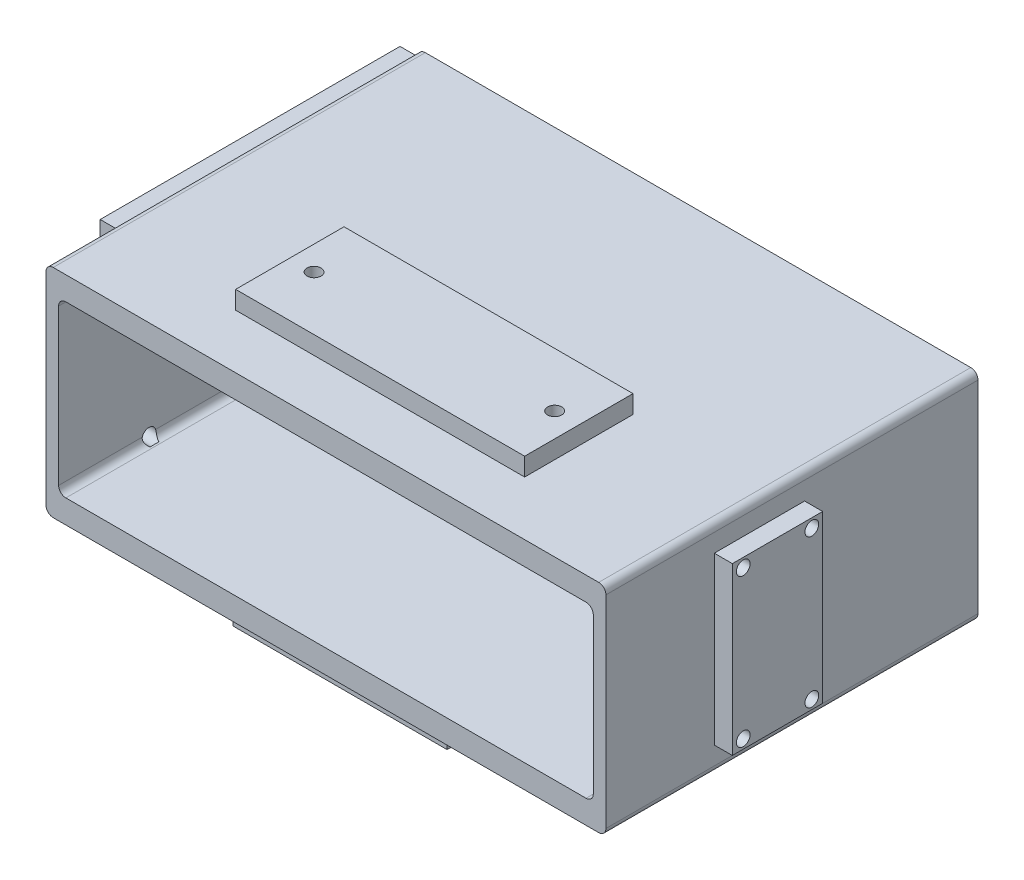
SolidWorks part; units mm, degrees
ref_plane "前视基准面" through (0, 0, 0) normal (0, 0, 1) x (1, 0, 0)
ref_plane "上视基准面" through (0, 0, 0) normal (0, 1, 0) x (1, 0, 0)
ref_plane "右视基准面" through (0, 0, 0) normal (1, 0, 0) x (0, 0, -1)
sketch "草图1" plane through (0, 0, 0) normal (0, 0, 1) x (1, 0, 0)
  line L1 (-77.5, -30) -> (77.5, -30)
  line L2 (-77.5, -30) -> (-77.5, 30)
  line L3 (-77.5, 30) -> (77.5, 30)
  line L4 (77.5, -30) -> (77.5, 30)
  line L5 (-77.5, -30) -> (77.5, 30) construction
  line L6 (-77.5, 30) -> (77.5, -30) construction
  point P0 (0, 0)
  dimension "D1" = 60
  dimension "D2" = 155
extrude "凸台-拉伸1" add sketch "草图1" along normal blind 3
sketch "草图2" plane through (0, 0, 3) normal (0, 0, 1) x (1, 0, 0)
  line L5 (-75.8502, 29.3614) -> (77.5, -30) construction
  line L6 (-81.3153, 0) -> (81.3153, 0) construction
  line L7 (-74, 23.5) -> (74, 23.5)
  line L8 (-74, 23.5) -> (-74, -23.5)
  line L9 (-74, -23.5) -> (74, -23.5)
  line L10 (74, 23.5) -> (74, -23.5)
  line L11 (-74, 23.5) -> (74, -23.5) construction
  line L12 (-74, -23.5) -> (74, 23.5) construction
  line L20 (77.5, -30) -> (77.5, 30)
  line L21 (77.5, 30) -> (-77.5, 30)
  line L22 (-77.5, 30) -> (-77.5, -30)
  line L23 (-77.5, -30) -> (77.5, -30)
  line L24 (77.5, -30) -> (77.5, 30)
  line L25 (77.5, 30) -> (-77.5, 30)
  line L26 (-77.5, 30) -> (-77.5, -30)
  line L27 (-77.5, -30) -> (77.5, -30)
  point P0 (0, 0)
  point P5 (0, 0)
  dimension "D1" = 148
  dimension "D2" = 47
  dimension "D3" = 0
extrude "凸台-拉伸2" add sketch "草图2" along normal blind 90
fillet "圆角1" radius 2 8 edges at (-77.5, 30, 46.5) (-77.5, -30, 46.5) (77.5, 30, 46.5) (77.5, -30, 46.5) (74, -23.5, 48) (-74, -23.5, 48) (74, 23.5, 48) (-74, 23.5, 48)
sketch "草图5" plane through (0, 0, 0) normal (0, 0, -1) x (-1, 0, 0)
  line L4 (77.5, -28) -> (77.5, 28)
  line L5 (75.5, 30) -> (-75.5, 30)
  line L6 (-77.5, 28) -> (-77.5, -28)
  line L7 (-75.5, -30) -> (75.5, -30)
  line L8 (77.5, -28) -> (77.5, 28)
  line L9 (75.5, 30) -> (-75.5, 30)
  line L10 (-77.5, 28) -> (-77.5, -28)
  line L11 (-75.5, -30) -> (75.5, -30)
  circle A0 centre (-60, 15) radius 1.9
  circle A1 centre (-60, -15) radius 1.9
  circle A2 centre (-30, 15) radius 1.9
  circle A3 centre (-30, -15) radius 1.9
  circle A4 centre (0, 15) radius 1.9
  arc A5 (77.5, 28) -> (75.5, 30) centre (75.5, 28) ccw
  arc A6 (-75.5, 30) -> (-77.5, 28) centre (-75.5, 28) ccw
  arc A7 (-77.5, -28) -> (-75.5, -30) centre (-75.5, -28) ccw
  arc A8 (75.5, -30) -> (77.5, -28) centre (75.5, -28) ccw
  arc A9 (77.5, 28) -> (75.5, 30) centre (75.5, 28) ccw
  arc A10 (-75.5, 30) -> (-77.5, 28) centre (-75.5, 28) ccw
  arc A11 (-77.5, -28) -> (-75.5, -30) centre (-75.5, -28) ccw
  arc A12 (75.5, -30) -> (77.5, -28) centre (75.5, -28) ccw
  circle A13 centre (0, -15) radius 1.9
  circle A14 centre (30, 15) radius 1.9
  circle A15 centre (30, -15) radius 1.9
  circle A16 centre (60, 15) radius 1.9
  circle A17 centre (60, -15) radius 1.9
  dimension "D1" = 3.8
  dimension "D4" = 17.5
  dimension "D3" = 15
  dimension "D6" = 30
  dimension "D8" = 30
  dimension "D2" = 0
  dimension "D5" = 2
  dimension "D7" = 5
extrude "切除-拉伸2" cut sketch "草图5" against normal blind 3 contours A0 | A1 | A3 | A2 | A4 | A13 | A14 | A15 | A16 | A17
sketch "草图6" plane through (-77.5, 0, 0) normal (-1, 0, 0) x (0, 0, 1)
  line L0 (93, 28) -> (93, -28) construction
  line L1 (24, -22) -> (68, -22)
  line L2 (24, -22) -> (24, 22)
  line L3 (24, 22) -> (68, 22)
  line L4 (68, -22) -> (68, 22)
  line L5 (24, -22) -> (68, 22) construction
  line L6 (24, 22) -> (68, -22) construction
  line L7 (93, 0) -> (0, 0)
  line L8 (0, 28) -> (0, -28) construction
  circle A0 centre (68, -22) radius 1.9
  circle A1 centre (68, 22) radius 1.9
  circle A2 centre (24, 22) radius 1.9
  circle A3 centre (24, -22) radius 1.9
  point P0 (46, 0)
  dimension "D4" = 3.8
  dimension "D5" = 3.8
  dimension "D6" = 3.8
  dimension "D7" = 3.8
  dimension "D1" = 44
  dimension "D2" = 44
  dimension "D3" = 25
extrude "切除-拉伸3" cut sketch "草图6" against normal blind 5 contours L4 A1 L3 | L3 A1 L4 | L3 A2 L2 | L2 A2 L3 | L1 A0 L4 | L4 A0 L1 | L2 A3 L1 | L1 A3 L2 region at (-77.5, -21.1936, 24.8064) region at (-77.5, -22.2688, 23.7312) region at (-77.5, -21.1936, 67.1936) region at (-77.5, -22.2688, 68.2688) region at (-77.5, 22.2688, 23.7312) region at (-77.5, 21.1936, 24.8064) region at (-77.5, 21.1936, 67.1936) region at (-77.5, 22.2688, 68.2688)
sketch "草图9" plane through (0, 0, 0) normal (0, 0, -1) x (-1, 0, 0)
  line L4 (77.5, -28) -> (77.5, 28)
  line L5 (75.5, 30) -> (-75.5, 30)
  line L6 (-77.5, 28) -> (-77.5, -28)
  line L7 (-75.5, -30) -> (75.5, -30)
  line L8 (77.5, -28) -> (77.5, 28)
  line L9 (75.5, 30) -> (-75.5, 30)
  line L10 (-77.5, 28) -> (-77.5, -28)
  line L11 (-75.5, -30) -> (75.5, -30)
  circle A1 centre (-60, 15) radius 1.9
  circle A2 centre (-60, 15) radius 1.9
  circle A3 centre (60, -15) radius 1.9
  circle A4 centre (60, -15) radius 1.9
  circle A5 centre (-60, -15) radius 1.9
  circle A6 centre (-60, -15) radius 1.9
  circle A7 centre (-30, -15) radius 1.9
  circle A8 centre (-30, -15) radius 1.9
  circle A9 centre (-30, 15) radius 1.9
  circle A10 centre (-30, 15) radius 1.9
  circle A11 centre (0, 15) radius 1.9
  circle A12 centre (0, 15) radius 1.9
  circle A13 centre (60, 15) radius 1.9
  circle A14 centre (60, 15) radius 1.9
  circle A15 centre (30, -15) radius 1.9
  circle A16 centre (30, -15) radius 1.9
  circle A17 centre (30, 15) radius 1.9
  circle A18 centre (30, 15) radius 1.9
  circle A19 centre (0, -15) radius 1.9
  circle A20 centre (0, -15) radius 1.9
  arc A24 (77.5, 28) -> (75.5, 30) centre (75.5, 28) ccw
  arc A25 (-75.5, 30) -> (-77.5, 28) centre (-75.5, 28) ccw
  arc A26 (-77.5, -28) -> (-75.5, -30) centre (-75.5, -28) ccw
  arc A27 (75.5, -30) -> (77.5, -28) centre (75.5, -28) ccw
  arc A28 (77.5, 28) -> (75.5, 30) centre (75.5, 28) ccw
  arc A29 (-75.5, 30) -> (-77.5, 28) centre (-75.5, 28) ccw
  arc A30 (-77.5, -28) -> (-75.5, -30) centre (-75.5, -28) ccw
  arc A31 (75.5, -30) -> (77.5, -28) centre (75.5, -28) ccw
  dimension "D1" = 0
  dimension "D2" = 0
  dimension "D3" = 0
  dimension "D4" = 0
  dimension "D5" = 0
  dimension "D6" = 0
  dimension "D7" = 0
  dimension "D8" = 0
  dimension "D9" = 0
  dimension "D10" = 0
  dimension "D11" = 0
extrude "凸台-拉伸3" add sketch "草图9" along normal blind 10
sketch "草图10" plane through (-77.5, 0, 0) normal (-1, 0, 0) x (0, 0, 1)
  line L0 (93, 28) -> (-10, 28) construction
  line L1 (73, 28) -> (-10, 28)
  line L2 (73, 28) -> (73, -28)
  line L3 (73, -28) -> (-10, -28)
  line L4 (-10, 28) -> (-10, -28)
  circle A0 centre (68, 22) radius 1.9 construction
  circle A2 centre (24, -22) radius 1.9
  circle A4 centre (24, -22) radius 1.9
  circle A6 centre (24, 22) radius 1.9
  circle A8 centre (24, 22) radius 1.9
  circle A10 centre (68, -22) radius 1.9
  circle A11 centre (68, -22) radius 1.9
  circle A12 centre (68, 22) radius 1.9
  circle A13 centre (68, 22) radius 1.9
  dimension "D1" = 5
  dimension "D2" = 0
  dimension "D3" = 0
  dimension "D4" = 0
  dimension "D5" = 0
extrude "凸台-拉伸4" add sketch "草图10" along normal blind 5
sketch "草图7" plane through (0, -30, 0) normal (0, -1, 0) x (1, 0, 0)
  line L0 (-75.5, 41.5) -> (75.5, 41.5)
  line L1 (-24.605, -3) -> (24.605, -3)
  line L2 (-24.605, -3) -> (-24.605, 84.08)
  line L3 (-24.605, 84.08) -> (24.605, 84.08)
  line L4 (24.605, -3) -> (24.605, 84.08)
  line L5 (-24.605, -3) -> (24.605, 84.08) construction
  line L6 (-24.605, 84.08) -> (24.605, -3) construction
  line L7 (-75.5, 93) -> (-75.5, -10) construction
  line L8 (75.5, -10) -> (75.5, 93) construction
  line L9 (75.5, -10) -> (-75.5, -10) construction
  line L12 (0, 93) -> (0, -10)
  line L13 (-75.5, 93) -> (75.5, 93) construction
  circle A0 centre (24.605, 84.08) radius 1.9
  circle A1 centre (-24.605, 84.08) radius 1.9
  circle A2 centre (-24.605, -3) radius 1.9
  circle A3 centre (24.605, -3) radius 1.9
  point P20 (0, 40.54)
  dimension "D3" = 3.8
  dimension "D4" = 3.8
  dimension "D5" = 3.8
  dimension "D6" = 3.8
  dimension "D1" = 87.08
  dimension "D2" = 49.21
  dimension "D7" = 7
extrude "切除-拉伸5" cut sketch "草图7" against normal blind 5 contours L3 A1 L2 | L2 A1 L3 | L3 A0 L4 | L4 A0 L3 | L2 A2 L1 | L1 A2 L2 | L1 A3 L4 | L4 A3 L1 region at (-23.7986, -30, -2.1936) region at (-24.8738, -30, -3.2688) region at (-24.8738, -30, 84.3488) region at (-23.7986, -30, 83.2736) region at (24.8738, -30, -3.2688) region at (23.7986, -30, -2.1936) region at (23.7986, -30, 83.2736) region at (24.8738, -30, 84.3488)
sketch "草图13" plane through (0, -30, 0) normal (0, -1, 0) x (1, 0, 0)
  line L0 (75.5, -10) -> (-75.5, -10) construction
  line L1 (-29.605, -10) -> (29.605, -10)
  line L2 (-29.605, -10) -> (-29.605, 89.08)
  line L3 (-29.605, 89.08) -> (29.605, 89.08)
  line L4 (29.605, -10) -> (29.605, 89.08)
  circle A0 centre (24.605, 84.08) radius 1.9 construction
  circle A1 centre (-24.605, 84.08) radius 1.9 construction
  circle A3 centre (-24.605, -3) radius 1.9
  circle A5 centre (-24.605, -3) radius 1.9
  circle A7 centre (24.605, -3) radius 1.9
  circle A9 centre (24.605, -3) radius 1.9
  circle A11 centre (24.605, 84.08) radius 1.9
  circle A12 centre (24.605, 84.08) radius 1.9
  circle A13 centre (-24.605, 84.08) radius 1.9
  circle A14 centre (-24.605, 84.08) radius 1.9
  dimension "D1" = 5
  dimension "D3" = 5
  dimension "D2" = 5
  dimension "D4" = 0
  dimension "D5" = 0
  dimension "D6" = 0
  dimension "D7" = 0
extrude "凸台-拉伸5" add sketch "草图13" along normal blind 5
sketch "草图15" plane through (0, 30, 0) normal (0, 1, 0) x (1, 0, 0)
  line L0 (-75.5, 10) -> (75.5, 10) construction
  line L1 (67.5, 10) -> (77.5, 10)
  line L2 (67.5, 10) -> (67.5, -93)
  line L3 (67.5, -93) -> (77.5, -93)
  line L4 (77.5, 10) -> (77.5, -93)
  dimension "D1" = 10
extrude "凸台-拉伸6" [suppressed] add sketch "草图15" along normal blind 10 and the other way blind 5
sketch "草图14" [suppressed] plane through (77.5, 0, 0) normal (1, 0, 0) x (0, 0, -1)
  line L0 (-41.5, -28) -> (-41.5, 40)
  line L1 (-74.85, -20.025) -> (-8.15, -20.025)
  line L2 (-74.85, -20.025) -> (-74.85, 32.025)
  line L3 (-74.85, 32.025) -> (-8.15, 32.025)
  line L4 (-8.15, -20.025) -> (-8.15, 32.025)
  line L5 (-74.85, -20.025) -> (-8.15, 32.025) construction
  line L6 (-74.85, 32.025) -> (-8.15, -20.025) construction
  line L7 (-93, -28) -> (10, -28) construction
  line L8 (-93, 40) -> (10, 40) construction
  line L9 (-93, 6) -> (10, 6)
  line L10 (-93, -28) -> (-93, 40) construction
  line L11 (10, 40) -> (10, -28) construction
  circle A0 centre (-74.85, -20.025) radius 1.9
  circle A1 centre (-74.85, 32.025) radius 1.9
  circle A2 centre (-8.15, 32.025) radius 1.9
  circle A3 centre (-8.15, -20.025) radius 1.9
  point P0 (-41.5, 6)
  dimension "D3" = 3.8
  dimension "D4" = 3.8
  dimension "D5" = 3.8
  dimension "D6" = 3.8
  dimension "D1" = 66.7
  dimension "D2" = 52.05
extrude "切除-拉伸6" [suppressed] cut sketch "草图14" against normal blind 5 contours L2 A0 L1 | L1 A0 L2 | L3 A1 L2 | L2 A1 L3 | L4 A3 L1 | L1 A3 L4 | L4 A2 L3 | L3 A2 L4
sketch "草图16" [suppressed] plane through (77.5, 0, 0) normal (1, 0, 0) x (0, 0, -1)
  line L0 (10, 40) -> (10, -28) construction
  line L1 (-79.85, 37.025) -> (10, 37.025)
  line L2 (-79.85, 37.025) -> (-79.85, -25.025)
  line L3 (-79.85, -25.025) -> (10, -25.025)
  line L4 (10, 37.025) -> (10, -25.025)
  circle A0 centre (-74.85, 32.025) radius 1.9 construction
  arc A1 (-76.0477, -21.5) -> (-73.6523, -21.5) centre (-74.85, -20.025) ccw construction
  circle A3 centre (-8.15, 32.025) radius 1.9
  circle A5 centre (-8.15, 32.025) radius 1.9
  circle A7 centre (-8.15, -20.025) radius 1.9
  circle A9 centre (-8.15, -20.025) radius 1.9
  circle A11 centre (-74.85, 32.025) radius 1.9
  circle A12 centre (-74.85, 32.025) radius 1.9
  circle A13 centre (-74.85, -20.025) radius 1.9
  circle A14 centre (-74.85, -20.025) radius 1.9
  dimension "D2" = 5
  dimension "D3" = 5
  dimension "D1" = 5
  dimension "D4" = 0
  dimension "D5" = 0
  dimension "D6" = 0
  dimension "D7" = 0
extrude "凸台-拉伸7" [suppressed] add sketch "草图16" along normal blind 5
sketch "草图17" [suppressed] plane through (0, 37.025, 0) normal (0, 1, 0) x (1, 0, 0)
  line L0 (67.5, -93) -> (-75.5, -93) construction
  line L1 (82.5, 10) -> (62.5, 10)
  line L2 (82.5, 10) -> (82.5, -93)
  line L3 (82.5, -93) -> (62.5, -93)
  line L4 (62.5, 10) -> (62.5, -93)
  line L5 (67.5, -93) -> (67.5, 10) construction
  dimension "D1" = 5
extrude "切除-拉伸7" [suppressed] cut sketch "草图17" along normal blind 5
fillet "圆角2" [suppressed] radius 2
sketch "草图18" plane through (77.5, 0, 0) normal (1, 0, 0) x (0, 0, -1)
  line L0 (10, 28) -> (-93, 28) construction
  line L1 (-63, 23) -> (-38, 23)
  line L2 (-63, 23) -> (-63, -23)
  line L3 (-63, -23) -> (-38, -23)
  line L4 (-38, 23) -> (-38, -23)
  line L5 (-93, -28) -> (10, -28) construction
  line L6 (-93, -28) -> (-93, 28) construction
  dimension "D1" = 5
  dimension "D2" = 5
  dimension "D3" = 30
  dimension "D4" = 25
extrude "凸台-拉伸8" add sketch "草图18" along normal blind 5
sketch "草图19" plane through (82.5, 0, 0) normal (1, 0, 0) x (0, 0, -1)
  line L1 (-60, 20.5) -> (-41, 20.5)
  line L2 (-60, 20.5) -> (-60, -20.5)
  line L3 (-60, -20.5) -> (-41, -20.5)
  line L4 (-41, 20.5) -> (-41, -20.5)
  line L5 (-63, -23) -> (-38, -23) construction
  line L7 (-38, -23) -> (-38, 23) construction
  circle A0 centre (-60, 20.5) radius 1.9
  circle A1 centre (-41, 20.5) radius 1.9
  circle A2 centre (-60, -20.5) radius 1.9
  circle A3 centre (-41, -20.5) radius 1.9
  dimension "D5" = 3.8
  dimension "D6" = 3.8
  dimension "D7" = 3.8
  dimension "D8" = 3.8
  dimension "D1" = 19
  dimension "D2" = 41
  dimension "D3" = 2.5
  dimension "D4" = 3
extrude "切除-拉伸8" cut sketch "草图19" against normal blind 10 contours L2 A2 L3 | L3 A2 L2 | L4 A3 L3 | L3 A3 L4 | L1 A0 L2 | L2 A0 L1 | L4 A1 L1 | L1 A1 L4 region at (82.5, 20.7688, 60.2688) region at (82.5, 19.6936, 59.1936) region at (82.5, 20.7688, 40.7312) region at (82.5, 19.6936, 41.8064) region at (82.5, -19.6936, 59.1936) region at (82.5, -20.7688, 60.2688) region at (82.5, -20.7688, 40.7312) region at (82.5, -19.6936, 41.8064)
sketch "草图21" plane through (0, 30, 0) normal (0, 1, 0) x (1, 0, 0)
  line L0 (0, 10) -> (0, -93)
  line L1 (-40, -78) -> (40, -78)
  line L2 (-40, -78) -> (-40, -48)
  line L3 (-40, -48) -> (40, -48)
  line L4 (40, -78) -> (40, -48)
  line L5 (0, -48) -> (0, -78) construction
  line L6 (-40, -63) -> (40, -63) construction
  line L7 (-75.5, 10) -> (75.5, 10) construction
  line L8 (75.5, -93) -> (-75.5, -93) construction
  point P0 (0, -63)
  dimension "D1" = 30
  dimension "D2" = 80
  dimension "D3" = 30
extrude "凸台-拉伸9" add sketch "草图21" along normal blind 5 contours L3 L2 L1 L0 | L1 L4 L3 L0 region at (20, 30, 63) region at (-20, 30, 63)
sketch "草图22" plane through (0, 35, 0) normal (0, 1, 0) x (1, 0, 0)
  line L0 (-40, -63) -> (40, -63)
  line L1 (-40, -78) -> (-40, -48) construction
  line L2 (40, -78) -> (40, -48) construction
  line L3 (-33.3, -63) -> (33.3, -63)
  line L4 (0, -48) -> (0, -78)
  line L5 (-40, -48) -> (40, -48) construction
  line L6 (-40, -78) -> (40, -78) construction
  circle A0 centre (-33.3, -63) radius 1.95
  circle A1 centre (33.3, -63) radius 1.95
  point P14 (0, -63)
  dimension "D3" = 3.9
  dimension "D4" = 3.9
  dimension "D1" = 33.3
  dimension "D2" = 33.3
extrude "切除-拉伸9" cut sketch "草图22" against normal blind 7 contours L0 A1 | L0 A1 | L0 A0 | L0 A0 region at (-33.3, 35, 62.1724) region at (-33.3, 35, 63.8276) region at (33.3, 35, 62.1724) region at (33.3, 35, 63.8276)
sketch "草图24" plane through (-82.5, 0, 0) normal (-1, 0, 0) x (0, 0, 1)
  line L0 (24, 22) -> (68, -22)
  line L2 (71, -25) -> (21, -25)
  line L3 (71, -25) -> (71, 25)
  line L4 (73, -28) -> (73, 28)
  line L5 (73, 28) -> (-10, 28)
  line L6 (-10, 28) -> (-10, -28)
  line L7 (-10, -28) -> (73, -28)
  line L8 (73, -28) -> (73, 28)
  line L9 (73, 28) -> (-10, 28)
  line L10 (-10, 28) -> (-10, -28)
  line L11 (-10, -28) -> (73, -28)
  line L12 (71, 25) -> (21, 25)
  line L13 (21, -25) -> (21, 25)
  line L14 (46, 25) -> (46, -25) construction
  line L15 (71, 0) -> (21, 0) construction
  line L16 (28.5, -25) -> (63.5, -25)
  line L17 (28.5, -25) -> (28.5, 25)
  line L18 (28.5, 25) -> (63.5, 25)
  line L19 (63.5, -25) -> (63.5, 25)
  line L20 (46, 25) -> (46, -25) construction
  line L21 (28.5, 0) -> (63.5, 0) construction
  line L22 (21, -17.5) -> (71, -17.5)
  line L23 (21, -17.5) -> (21, 17.5)
  line L24 (21, 17.5) -> (71, 17.5)
  line L25 (71, -17.5) -> (71, 17.5)
  line L26 (46, 17.5) -> (46, -17.5) construction
  line L27 (21, 0) -> (71, 0) construction
  circle A1 centre (24, -22) radius 1.9
  circle A2 centre (24, -22) radius 1.9
  circle A3 centre (24, 22) radius 1.9
  circle A4 centre (24, 22) radius 1.9
  circle A5 centre (68, -22) radius 1.9
  circle A6 centre (68, -22) radius 1.9
  circle A7 centre (68, 22) radius 1.9
  circle A8 centre (68, 22) radius 1.9
  point P14 (46, 0)
  point P16 (46, 0)
  point P21 (46, 0)
  point P25 (46, 0)
  dimension "D6" = 50
  dimension "D7" = 50
  dimension "D8" = 35
  dimension "D9" = 35
  dimension "D1" = 0
  dimension "D2" = 0
  dimension "D3" = 0
  dimension "D4" = 0
  dimension "D5" = 0
extrude "切除-拉伸10" cut sketch "草图24" against normal blind 5 contours L24 L13 L22 L17 | L17 L22 L0 | L24 L0 L19 | L17 L24 L19 L12 | L24 L19 L22 L3 | L22 L17 L2 L19 region at (-82.5, 21.25, 46) region at (-82.5, 5.8333, 51.8333) region at (-82.5, -5.8333, 40.1667) region at (-82.5, 0, 24.75) region at (-82.5, -21.25, 46) region at (-82.5, 0, 67.25)
sketch "草图20" plane through (0, 30, 0) normal (0, 1, 0) x (1, 0, 0)
  line L0 (-75.5, -63) -> (75.5, -63)
  line L1 (-75.5, 10) -> (-75.5, -93) construction
  line L2 (75.5, -93) -> (75.5, 10) construction
  line L3 (-33.3, -63) -> (33.3, -63)
  line L7 (75.5, -93) -> (75.5, 10)
  line L8 (75.5, 10) -> (-75.5, 10)
  line L9 (-75.5, 10) -> (-75.5, -93)
  line L10 (-75.5, -93) -> (75.5, -93)
  line L11 (75.5, -93) -> (75.5, 10)
  line L12 (75.5, 10) -> (-75.5, 10)
  line L13 (-75.5, 10) -> (-75.5, -93)
  line L14 (-75.5, -93) -> (75.5, -93)
  circle A0 centre (-33.3, -63) radius 2.3686
  circle A1 centre (33.3, -63) radius 2.6414
  point P8 (0, -63)
  dimension "D2" = 30
  dimension "D3" = 33.3
  dimension "D4" = 33.3
  dimension "D1" = 0
sketch "草图26" plane through (0, 0, 93) normal (0, 0, 1) x (1, 0, 0)
  line L1 (72, 23.5) -> (-72, 23.5) construction
  line L2 (72, 23.5) -> (-72, 23.5)
  line L3 (-74, 21.5) -> (-74, -21.5) construction
  line L4 (-74, 21.5) -> (-74, -21.5)
  line L5 (-72, -23.5) -> (72, -23.5) construction
  line L6 (-72, -23.5) -> (72, -23.5)
  line L7 (75.5, 30) -> (-75.5, 30)
  line L8 (-77.5, 28) -> (-77.5, -28)
  line L9 (-75.5, -30) -> (75.5, -30)
  line L10 (77.5, -28) -> (77.5, 28)
  line L11 (75.5, 30) -> (-75.5, 30)
  line L12 (-77.5, 28) -> (-77.5, -28)
  line L13 (-75.5, -30) -> (75.5, -30)
  line L14 (77.5, -28) -> (77.5, 28)
  line L15 (74, -21.5) -> (74, 21.5) construction
  line L16 (74, -21.5) -> (74, 21.5)
  arc A0 (-72, 23.5) -> (-74, 21.5) centre (-72, 21.5) ccw construction
  arc A1 (-72, 23.5) -> (-74, 21.5) centre (-72, 21.5) ccw
  arc A4 (-75.5, 30) -> (-77.5, 28) centre (-75.5, 28) ccw
  arc A5 (-77.5, -28) -> (-75.5, -30) centre (-75.5, -28) ccw
  arc A6 (75.5, -30) -> (77.5, -28) centre (75.5, -28) ccw
  arc A7 (77.5, 28) -> (75.5, 30) centre (75.5, 28) ccw
  arc A8 (-75.5, 30) -> (-77.5, 28) centre (-75.5, 28) ccw
  arc A9 (-77.5, -28) -> (-75.5, -30) centre (-75.5, -28) ccw
  arc A10 (75.5, -30) -> (77.5, -28) centre (75.5, -28) ccw
  arc A11 (77.5, 28) -> (75.5, 30) centre (75.5, 28) ccw
  dimension "D1" = 0
